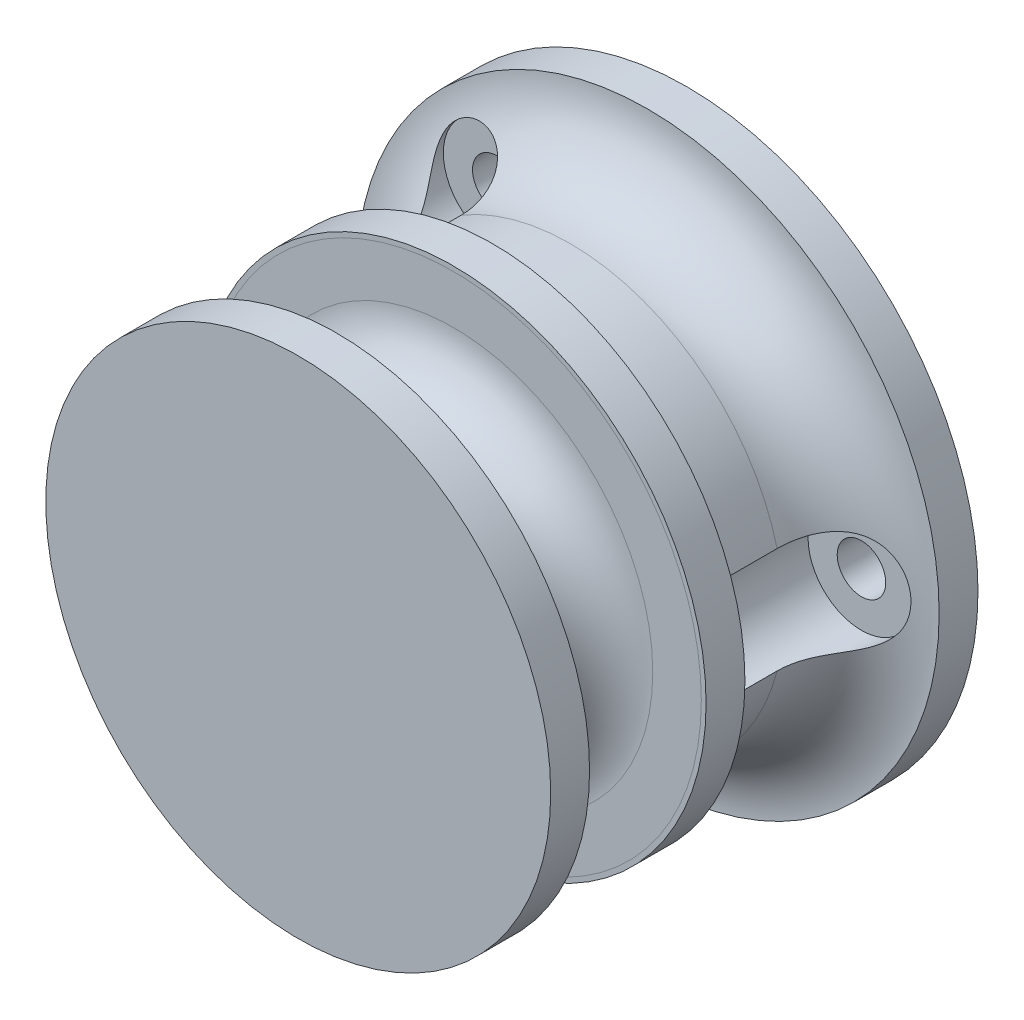
SolidWorks part; units mm, degrees
ref_plane "정면" through (0, 0, 0) normal (0, 0, 1) x (1, 0, 0)
ref_plane "윗면" through (0, 0, 0) normal (0, 1, 0) x (1, 0, 0)
ref_plane "우측면" through (0, 0, 0) normal (1, 0, 0) x (0, 0, -1)
sketch "스케치1" plane through (0, 0, 0) normal (0, 0, 1) x (1, 0, 0)
  circle A0 centre (0, 0) radius 15
  dimension "D1" = 30
extrude "보스-돌출1" add sketch "스케치1" along normal blind 10 contours A0
sketch "스케치2" plane through (0, 0, 0) normal (0, 0, -1) x (-1, 0, 0)
  circle A0 centre (0, 0) radius 5.25
  dimension "D1" = 10.5
sketch "스케치3" plane through (0, 0, 2.3) normal (0, 0, 1) x (1, 0, 0)
  circle A0 centre (0, 0) radius 2.85
  dimension "D1" = 5.7
extrude "컷-돌출1" cut sketch "스케치3" along normal blind 3.1
extrude "컷-돌출2" cut sketch "스케치2" against normal blind 2.4
sketch "스케치4" plane through (0, 0, 0) normal (0, 0, -1) x (-1, 0, 0)
  circle A2 centre (0, 11) radius 1.25
  circle A3 centre (7.7782, 7.7782) radius 1.25
  circle A4 centre (11, 0) radius 1.25
  circle A5 centre (7.7782, -7.7782) radius 1.25
  circle A6 centre (0, -11) radius 1.25
  circle A7 centre (-7.7782, -7.7782) radius 1.25
  circle A8 centre (-11, 0) radius 1.25
  circle A9 centre (-7.7782, 7.7782) radius 1.25
  point P22 (0, 0)
  dimension "D1" = 8
  dimension "D2" = 2.5
sketch "스케치5" plane through (0, 0, 10) normal (0, 0, 1) x (1, 0, 0)
  circle A0 centre (0, 0) radius 13
extrude "보스-돌출2" add sketch "스케치5" along normal blind 10
sketch "스케치10" plane through (0, 0, 0) normal (0, 1, 0) x (1, 0, 0)
  line L0 (15, -18) -> (15, -12)
  line L1 (10.2544, -18) -> (15, -18)
  line L2 (15, -10) -> (15, 0) construction
  line L3 (10.2544, -12) -> (12.7544, -12)
  line L6 (15, -12) -> (12.7544, -12)
  arc A0 (10.2544, -12) -> (10.2544, -18) centre (10.2544, -15) ccw
  point P0 (12.7544, -15)
  point P5 (12.7544, -15)
sweep "컷-스윕2" cut profiles "스케치10" path edge at (13, 0, 20)
sketch "스케치11" plane through (0, 0, 0) normal (0, 1, 0) x (1, 0, 0)
  line L1 (15, -10) -> (15, 0) construction
  line L3 (15, -2) -> (15, -10)
  line L4 (15, -2) -> (11, -2)
  line L5 (15, -10) -> (11, -10)
  line L6 (11, -2) -> (11, -10)
  dimension "D1" = 4
sweep "컷-스윕3" cut profiles "스케치11" path edge at (15, 0, 10)
fillet "필렛3" radius 4 1 edges at (-11, 0, 2)
extrude "컷-돌출4" cut sketch "스케치4" against normal blind 2
sketch "스케치12" plane through (0, 0, 2) normal (0, 0, -1) x (-1, 0, 0)
  circle A2 centre (-11, 0) radius 2.75
  circle A5 centre (7.7782, 7.7782) radius 2.75
  circle A6 centre (11, 0) radius 2
  circle A7 centre (7.7782, -7.7782) radius 2.75
  point P19 (0, 0)
  dimension "D1" = 5.5
  dimension "D2" = 5.5
  dimension "D3" = 4
  dimension "D4" = 5.5
extrude "컷-돌출5" cut sketch "스케치12" against normal blind 8
sketch "스케치26" plane through (0, 0, 0) normal (0, 1, 0) x (1, 0, 0)
  line L5 (-14.2919, -6) -> (-4.2919, -6)
  line L6 (-14.2919, -6) -> (-14.2919, -9)
  line L7 (-14.2919, -9) -> (-4.2919, -9)
  line L8 (-4.2919, -6) -> (-4.2919, -9)
extrude "컷-돌출6" cut sketch "스케치26" against normal mid plane 5
sketch "스케치28" plane through (0, 0, 0) normal (0, 1, 0) x (1, 0, 0)
  line L0 (-11, -2) -> (-11, -6.5336)
  line L1 (-12.25, -2) -> (-9.75, -2) construction
  line L2 (-9.9941, -7.5336) -> (-5.3936, -7.5065)
  line L3 (-4.2919, -9) -> (-4.2919, -6) construction
  line L4 (6.9718, -14.5576) -> (-3.8079, -7.9488)
  line L5 (-11, -2) -> (-11, 0)
  line L6 (10.2544, -15) -> (8.5398, -15)
  arc A0 (-5.3936, -7.5065) -> (-3.8079, -7.9488) centre (-5.3759, -10.5064) cw
  arc A1 (-11, -6.5336) -> (-9.9941, -7.5336) centre (-10, -6.5336) ccw
  arc A2 (8.5398, -15) -> (6.9718, -14.5576) centre (8.5398, -12) cw
  point P10 (-4.2919, -7.5)
  dimension "D1" = 3
sketch "스케치29" plane through (0, 0, 0) normal (0, 0, 1) x (1, 0, 0)
  circle A0 centre (-11, 0) radius 0.8
sweep "컷-스윕30" cut profiles "스케치29" path "스케치28"
fillet "필렛4" radius 0.5 4 edges at (4.2095, 10.1627, 10) (4.2095, -10.1627, 10) (-10.301, -3.8586, 10) (-10.301, 3.8586, 10)
sketch "스케치30" plane through (0, 0, 0) normal (0, 0, -1) x (-1, 0, 0)
  circle A0 centre (0, -11) radius 1.25
  circle A1 centre (-7.7782, -7.7782) radius 1.25
  circle A2 centre (0, 11) radius 1.25
  circle A4 centre (-7.7782, 7.7782) radius 1.25
extrude "보스-돌출3" add sketch "스케치30" against normal blind 2
